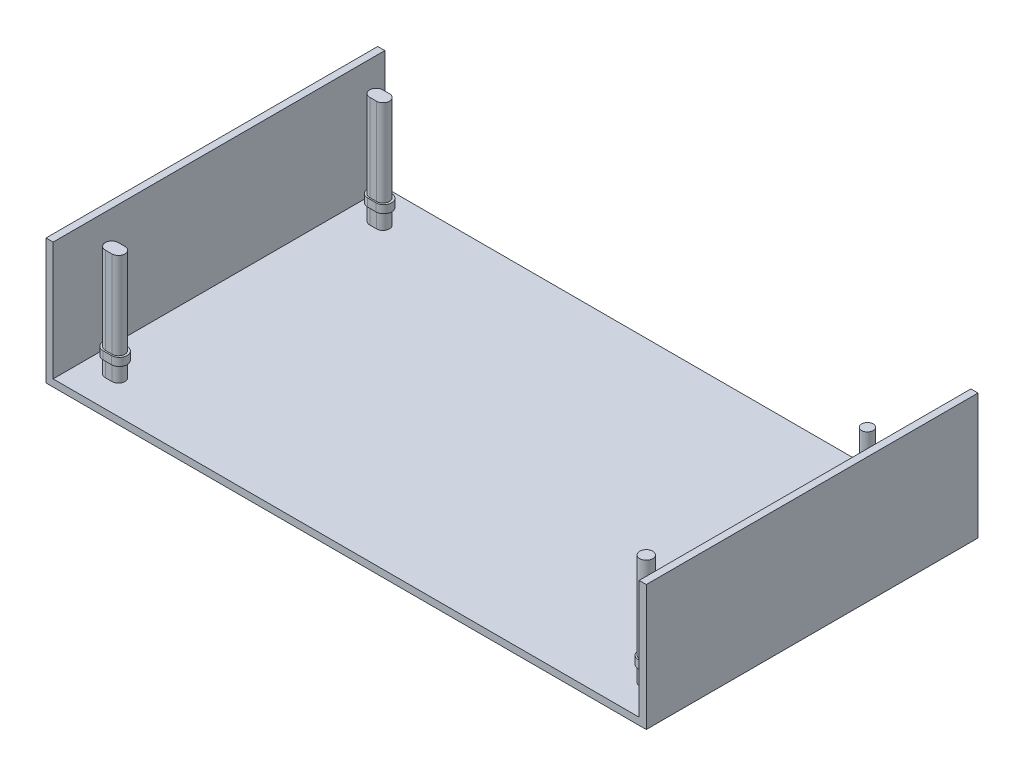
SolidWorks part; units mm, degrees
ref_plane "前视基准面" through (0, 0, 0) normal (0, 0, 1) x (1, 0, 0)
ref_plane "上视基准面" through (0, 0, 0) normal (0, 1, 0) x (1, 0, 0)
ref_plane "右视基准面" through (0, 0, 0) normal (1, 0, 0) x (0, 0, -1)
other "Configuration Table"
sketch "草图1" plane through (0, 0, 0) normal (0, 1, 0) x (1, 0, 0)
  line L0 (0, 0) -> (152, 0)
  line L1 (152, 0) -> (152, 84)
  line L2 (152, 84) -> (0, 84)
  line L3 (0, 84) -> (0, 0)
  line L4 (76, 0) -> (76, 84) construction
  line L5 (152, 42) -> (140.5458, 42) construction
  point P12 (76, 4.5)
  point P15 (4.5, 42)
  point P16 (147.5, 42)
  dimension "D1" = 152
  dimension "D2" = 84
extrude "凸台-拉伸1" add sketch "草图1" along normal blind 1.8 contours L3 L0 L1 L2
sketch "草图2" plane through (0, 1.8, 0) normal (0, 1, 0) x (1, 0, 0)
  line L0 (76, 84) -> (76, 77.8584) construction
  line L2 (152, 42) -> (146.9312, 42) construction
  point P1 (0, 0)
sketch "草图3" plane through (0, 1.8, 0) normal (0, 1, 0) x (1, 0, 0)
  line L0 (76, 200084) -> (76, -199922.1416) construction
  line L1 (147.5, 79.5) -> (4.5, 79.5) construction
  line L2 (147.5, 79.5) -> (147.5, 4.5) construction
  line L3 (147.5, 4.5) -> (4.5, 4.5) construction
  line L4 (4.5, 79.5) -> (4.5, 4.5) construction
  line L5 (200152, 42) -> (-199853.0688, 42) construction
  line L6 (8.15, 8.5) -> (9.85, 8.5) construction
  line L7 (8.15, 10.14) -> (9.85, 10.14)
  line L8 (8.15, 6.86) -> (9.85, 6.86)
  line L9 (4.5, 41.99) -> (9.85, 41.99) construction
  line L10 (8.15, 75.48) -> (9.85, 75.48) construction
  line L11 (8.15, 73.84) -> (9.85, 73.84)
  line L12 (8.15, 77.12) -> (9.85, 77.12)
  arc A0 (8.15, 10.14) -> (8.15, 6.86) centre (8.15, 8.5) ccw
  arc A1 (9.85, 6.86) -> (9.85, 10.14) centre (9.85, 8.5) ccw
  arc A2 (8.15, 73.84) -> (8.15, 77.12) centre (8.15, 75.48) cw
  arc A3 (9.85, 77.12) -> (9.85, 73.84) centre (9.85, 75.48) cw
  circle A4 centre (143.5, 8.5) radius 1.64
  circle A5 centre (143.5, 64.5) radius 1.4621
  point P6 (76, 4.5)
  point P7 (147.5, 42)
  point P12 (9, 8.5)
  point P21 (9, 75.48)
  dimension "D9" = 3.28
  dimension "D1" = 143
  dimension "D2" = 75
  dimension "D3" = 3.28
  dimension "D4" = 1.7
  dimension "D5" = 4
  dimension "D6" = 4.5
  dimension "D7" = 4
  dimension "D8" = 4
  dimension "D10" = 4
  dimension "D11" = 15
extrude "凸台-拉伸2" add sketch "草图3" along normal blind 28
extrude "凸台-拉伸3" add sketch "草图3<2>" along normal blind 4.5
sketch "草图3<2>" plane through (0, 1.8, 0) normal (0, 1, 0) x (1, 0, 0) same geometry as "草图3"
sketch "草图4" plane through (0, 29.8, 0) normal (0, 1, 0) x (1, 0, 0)
  line L0 (7.9522, 8.5) -> (10.0478, 8.5) construction
  line L1 (7.9522, 10.5) -> (10.0478, 10.5)
  line L2 (7.9522, 6.5) -> (10.0478, 6.5)
  line L3 (0, 42) -> (2.7094, 42) construction
  line L6 (7.9522, 75.5) -> (10.0478, 75.5) construction
  line L7 (7.9522, 73.5) -> (10.0478, 73.5)
  line L8 (7.9522, 77.5) -> (10.0478, 77.5)
  arc A0 (7.9522, 10.5) -> (7.9522, 6.5) centre (7.9522, 8.5) ccw
  arc A1 (10.0478, 6.5) -> (10.0478, 10.5) centre (10.0478, 8.5) ccw
  arc A2 (7.9522, 73.5) -> (7.9522, 77.5) centre (7.9522, 75.5) cw
  arc A3 (10.0478, 77.5) -> (10.0478, 73.5) centre (10.0478, 75.5) cw
  circle A4 centre (143.5, 64.5) radius 2
  circle A5 centre (143.5, 8.5) radius 2
  point P2 (9, 8.5)
  point P11 (9, 75.5)
  dimension "D1" = 2
  dimension "D2" = 4
  dimension "D3" = 4
extrude "凸台-拉伸4" add sketch "草图4" along normal blind 2 from offset 24 offset against normal yes
ref_plane "基准面1" through (0, 4.5, 0) normal (0, 1, 0) x (1, 0, 0)
sketch "草图10" plane through (0, 1.8, 0) normal (0, 1, 0) x (1, 0, 0)
  line L0 (0, 84) -> (1.8, 84)
  line L1 (152, 84) -> (0, 84) construction
  line L2 (0, 84) -> (0, 0)
  line L3 (0, 0) -> (1.8, 0)
  line L4 (0, 0) -> (152, 0) construction
  line L5 (1.8, 0) -> (1.8, 84)
  line L6 (76, 84) -> (76, 78.285) construction
  line L8 (152, 0) -> (150.2, 0)
  line L9 (152, 84) -> (152, 0)
  line L10 (152, 84) -> (150.2, 84)
  line L11 (150.2, 0) -> (150.2, 84)
  dimension "D1" = 1.8
extrude "凸台-拉伸6" add sketch "草图10" along normal blind 30
sketch "草图11" plane through (0, 1.8, 0) normal (0, 1, 0) x (1, 0, 0)
  line L0 (200152, 42) -> (-199853.0688, 42) construction
  line L1 (4.5, 79.5) -> (147.5, 79.5)
  line L2 (4.5, 79.5) -> (4.5, 4.5)
  line L3 (4.5, 4.5) -> (147.5, 4.5)
  line L4 (147.5, 79.5) -> (147.5, 4.5)
  line L5 (76, 200084) -> (76, -199922.1416) construction
  point P4 (147.5, 42)
  point P7 (76, 4.5)
  dimension "D1" = 143
  dimension "D2" = 75
